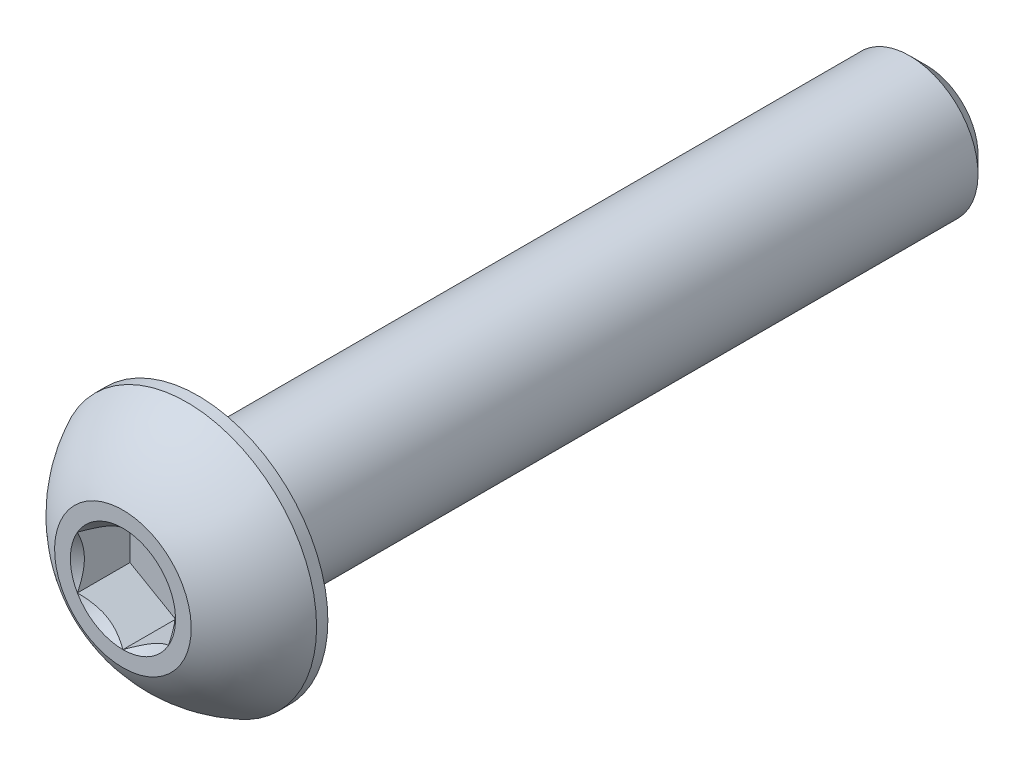
SolidWorks part; units mm, degrees
ref_plane "Front" through (0, 0, 0) normal (0, 0, 1) x (1, 0, 0)
ref_plane "Top" through (0, 0, 0) normal (0, 1, 0) x (1, 0, 0)
ref_plane "Right" through (0, 0, 0) normal (1, 0, 0) x (0, 0, -1)
sketch "Sketch1" plane through (0, 0, 0) normal (1, 0, 0) x (0, 0, -1)
  line L2 (1.65, 1.5) -> (17.65, 1.5)
  line L3 (17.65, 1.5) -> (17.65, 0)
  line L4 (17.65, 0) -> (1.65, 0)
  line L6 (1.4025, 2.85) -> (1.65, 2.85) construction
  line L7 (17.65, 1.5) -> (17.65, -1.5) construction
  line L8 (0, 0) -> (1.65, 0) construction
  line L9 (1.65, 2.85) -> (1.65, -2.85) construction
  line L11 (1.65, 1.5) -> (1.65, 0)
  line L13 (0, 1) -> (0, -1) construction
  line L14 (0, 1) -> (0, 1.5) construction
  line L15 (17.65, -1.5) -> (17.15, -1.5) construction
  arc A3 (0, 1.5) -> (1.4025, 2.85) centre (2.7948, 0) cw construction
  dimension "D1" = 0.2475
  dimension "Pitch" = 0.5
revolve "Revolve1" add sketch "Sketch1" angle 360 mid plane about L4
sketch "Sketch7" plane through (0, 0, 0) normal (1, 0, 0) x (0, 0, -1)
  line L6 (1.4025, 2.85) -> (1.65, 2.85) construction
  line L8 (0, 0) -> (1.65, 0) construction
  line L11 (1.65, 2.85) -> (1.65, -2.85) construction
  line L12 (1.4025, 2.85) -> (1.65, 2.85)
  line L13 (0, 0) -> (1.65, 0)
  line L14 (0, 1) -> (0, -1) construction
  line L15 (1.65, 2.85) -> (1.65, 0)
  line L16 (0, 1.5) -> (0, 0)
  arc A2 (1.4025, 2.85) -> (0, 1.5) centre (2.7948, 0) ccw construction
  arc A3 (1.4025, 2.85) -> (0, 1.5) centre (2.7948, 0) ccw
revolve "Revolve2" add sketch "Sketch7" angle 360 mid plane about L13
sketch "Sketch5" plane through (0, 0, 0) normal (0, 0, 1) x (1, 0, 0)
  line L1 (1, -0.5774) -> (1, 0.5774)
  line L2 (1, 0.5774) -> (0, 1.1547)
  line L3 (0, 1.1547) -> (-1, 0.5774)
  line L4 (-1, 0.5774) -> (-1, -0.5774)
  line L5 (-1, -0.5774) -> (0, -1.1547)
  line L6 (0, -1.1547) -> (1, -0.5774)
  circle A0 centre (0, 0) radius 1 construction
extrude "Cut-Extrude2" cut sketch "Sketch5" against normal blind 1.155
sketch "Sketch6" plane through (0, 0, 0) normal (0, 0, 1) x (1, 0, 0)
  circle A0 centre (0, 0) radius 1.1547
extrude "Cut-Extrude3" cut sketch "Sketch6" against normal blind 1.155 draft 45
sketch "Sketch11" plane through (0, 0, 0) normal (1, 0, 0) x (0, 0, -1)
  line L0 (1.65, -2.85) -> (1.65, 2.85)
  point P4 (1.65, 0)
split "Split1" trim tools "Sketch11" bodies to split 113 resulting bodies 119 120
sketch "Sketch10" plane through (0, 0, 0) normal (1, 0, 0) x (0, 0, -1)
  line L0 (17.65, 1.5) -> (17.65, -1.5) construction
  point P0 (16.9, -1.5)
  dimension "D1" = 0.75
sketch "Sketch3" [suppressed] plane through (0, 0, -17.65) normal (0, 0, -1) x (-1, 0, 0)
  circle A0 centre (0, 0) radius 1.5
curve "Helix/Spiral1" [suppressed] pitch 0.5 height 16.5 turns 33
sketch "Sketch2" [suppressed] plane through (0, 0, 0) normal (1, 0, 0) x (0, 0, -1)
  line L0 (17.6187, 1.5541) -> (18.1187, 1.5541) construction
  line L1 (18.1187, 1.5541) -> (17.8687, 1.1211) construction
  line L2 (17.8687, 1.1211) -> (17.6187, 1.5541) construction
  line L3 (17.8687, 1.5541) -> (17.8687, 1.5) construction
  line L4 (17.8687, 1.5) -> (17.8687, 1.1752) construction
  line L5 (17.8687, 1.1752) -> (17.8687, 1.1211) construction
  line L6 (17.8375, 1.1752) -> (17.9, 1.1752)
  line L7 (17.65, 1.5) -> (18.0875, 1.5) construction
  line L8 (17.6344, 1.5271) -> (18.1031, 1.5271)
  line L9 (17.6344, 1.5271) -> (17.8375, 1.1752)
  line L10 (18.1031, 1.5271) -> (17.9, 1.1752)
  point P10 (17.8687, 1.1752)
  point P13 (17.8687, 1.5)
  point P16 (17.8687, 1.5271)
  dimension "D1" = 0.5
  dimension "D2" = 0.0625
chamfer "Chamfer1" distance 0.375 angle 45 1 edges at (0, 1.5, -17.65)
sweep "Cut-Sweep1" [suppressed] cut profiles "Sketch2" path "Helix/Spiral1"
combine bodies "Combine1" [suppressed] operation type add bodies to combine 120 114
equation "\"D3@Helix/Spiral1\" = \"Lg@Sketch1\" + \"D4@Helix/Spiral1\""
equation "\"D1@Chamfer1\" = \"D4@Helix/Spiral1\" * .75"
equation "\"D1@Cut-Extrude2\" = \"Head Ht@Sketch1\" * .7"
equation "\"D1@Sketch1\" = \"Head Ht@Sketch1\" * .15"
equation "\"D1@Sketch10\" = \"D4@Helix/Spiral1\" * 1.5"
equation "\"D1@Cut-Extrude3\" = \"D1@Cut-Extrude2\""
equation "\"D4@Helix/Spiral1\"=\"Pitch@Sketch1\""
equation "\"D1@Sketch2\"=\"Pitch@Sketch1\""
equation "\"D2@Sketch2\"=\"D1@Sketch2\"/8"
